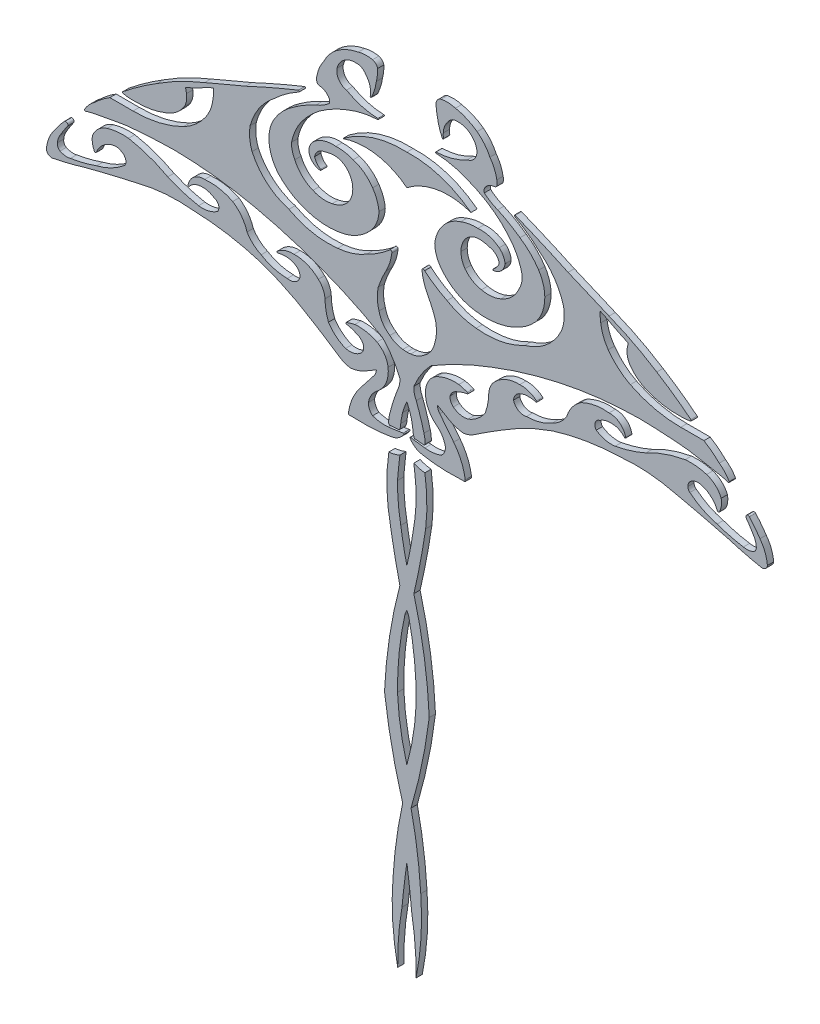
SolidWorks part; units mm, degrees
ref_plane "Front Plane" through (0, 0, 0) normal (0, 0, 1) x (1, 0, 0)
ref_plane "Top Plane" through (0, 0, 0) normal (0, 1, 0) x (1, 0, 0)
ref_plane "Right Plane" through (0, 0, 0) normal (1, 0, 0) x (0, 0, -1)
sketch "Sketch1" plane through (0, 0, 0) normal (0, 0, 1) x (1, 0, 0)
  line L0 (-378.0119, -291.6757) -> (723.9881, -291.6757) construction
  line L1 (0, 181.751) -> (0, -1116.5704) construction
  arc A0 (0, 0) -> (-102.3189, 16.8185) centre (-66.4769, -84.7774) ccw
  arc A1 (-102.3189, 16.8185) -> (0, 49.2353) centre (-6.7694, -107.0837) cw
  arc A2 (-46.483, 72.6334) -> (-96.5623, 86.847) centre (-42.9515, 180.406) cw
  arc A3 (-96.5623, 86.847) -> (-111.4389, 109.7382) centre (-92.7564, 105.6) cw
  arc A4 (-111.4389, 109.7382) -> (-82.2435, 131.9754) centre (-82.989, 102.6702) cw
  arc A5 (-82.2435, 131.9754) -> (-65.2385, 123.0329) centre (-80.0803, 115.4492) cw
  arc A6 (-65.2385, 123.0329) -> (-58.1804, 104.9836) centre (-86.4069, 104.3505) cw
  arc A7 (-58.1804, 104.9836) -> (-58.5682, 97.2174) centre (-81.9092, 102.2759) cw
  arc A8 (-58.5682, 97.2174) -> (-56.4425, 97.2174) centre (-57.5054, 97.2174) ccw
  arc A9 (-56.4425, 97.2174) -> (-48.7691, 122.5661) centre (-133.535, 134.3902) ccw
  arc A10 (-48.7691, 122.5661) -> (-46.7767, 141.444) centre (-115.5182, 139.1549) ccw
  arc A11 (-46.7767, 141.444) -> (-54.7054, 149.7875) centre (-57.8622, 138.8487) ccw
  arc A12 (-54.7054, 149.7875) -> (-77.6132, 148.8108) centre (-64.0956, 100.8971) ccw
  arc A13 (-112.1193, 133.6364) -> (-77.6132, 148.8108) centre (-61.5639, 65.4951) cw
  arc A14 (-112.1193, 133.6364) -> (-132.6666, 108.4613) centre (-72.6732, 80.4688) ccw
  arc A15 (-132.6666, 108.4613) -> (-143.7211, 82.666) centre (-82.6313, 71.7525) ccw
  arc A16 (-143.7211, 82.666) -> (-143.3742, 73.2976) centre (-127.6335, 78.571) ccw
  arc A17 (-143.3742, 73.2976) -> (-137.048, 71.0587) centre (-137.4037, 80.1106) ccw
  arc A18 (-137.048, 71.0587) -> (-126.2748, 64.5384) centre (-141.3136, 51.8507) cw
  arc A19 (-126.2748, 64.5384) -> (-123.7556, 54.7168) centre (-132.7532, 57.6428) cw
  arc A20 (-123.7556, 54.7168) -> (-145.0294, 41.952) centre (-168.0022, 104.3484) cw
  arc A21 (-145.0294, 41.952) -> (-180.6885, 21.1157) centre (-57.2788, -149.1556) ccw
  arc A22 (-180.6885, 21.1157) -> (-210.51, -8.7424) centre (-124.3326, -64.9924) ccw
  arc A23 (-210.51, -8.7424) -> (-220.3219, -40.8055) centre (-159.94, -41.7507) ccw
  arc A24 (-220.3219, -40.8055) -> (-206.0173, -82.3392) centre (-155.8049, -41.8154) ccw
  arc A25 (-206.0173, -82.3392) -> (-171.1908, -107.3688) centre (-131.9958, -16.0886) ccw
  arc A26 (-171.1908, -107.3688) -> (-108.8299, -115.592) centre (-126.2265, -6.9498) ccw
  arc A27 (-108.8299, -115.592) -> (-57.2788, -87.3333) centre (-119.7423, -34.5346) ccw
  arc A28 (-57.2788, -87.3333) -> (-44.4934, -55.3678) centre (-95.762, -53.4012) ccw
  arc A29 (-44.4934, -55.3678) -> (-54.7054, -27.6212) centre (-102.7057, -61.04) ccw
  arc A30 (-54.7054, -27.6212) -> (-85.7618, -4.1993) centre (-103.0408, -59.4111) ccw
  arc A31 (-85.7618, -4.1993) -> (-113.4484, 0.522) centre (-110.5767, -66.1782) ccw
  arc A32 (-113.4484, 0.522) -> (-147.4372, -9.344) centre (-118.1047, -46.9163) ccw
  arc A33 (-147.4372, -9.344) -> (-156.6796, -26.9832) centre (-132.5866, -28.3663) ccw
  arc A34 (-156.6796, -26.9832) -> (-148.8885, -41.1174) centre (-136.5721, -25.1138) ccw
  arc A35 (-148.8885, -41.1174) -> (-138.6418, -45.2059) centre (-138.1949, -29.2014) ccw
  arc A36 (-138.6418, -45.2059) -> (-137.9867, -43.384) centre (-138.3143, -44.295) ccw
  arc A37 (-137.9867, -43.384) -> (-147.4372, -30.7709) centre (-125.2796, -24.0161) cw
  arc A38 (-147.4372, -30.7709) -> (-131.9958, -16.0886) centre (-129.3273, -34.3561) cw
  arc A39 (-131.9958, -16.0886) -> (-115.5182, -13.2218) centre (-113.7987, -71.8932) cw
  arc A40 (-115.5182, -13.2218) -> (-95.3685, -21.9336) centre (-116.1464, -42.3331) cw
  arc A41 (-95.3685, -21.9336) -> (-86.4069, -45.0164) centre (-119.862, -44.7238) cw
  arc A42 (-86.4069, -45.0164) -> (-92.7564, -65.592) centre (-121.6366, -45.4124) cw
  arc A43 (-92.7564, -65.592) -> (-119.1175, -81.6215) centre (-126.143, -40.377) cw
  arc A44 (-119.1175, -81.6215) -> (-150.1147, -78.7107) centre (-130.2753, -33.9405) cw
  arc A45 (-150.1147, -78.7107) -> (-179.0485, -50.7531) centre (-130.1774, -29.1264) cw
  arc A46 (-179.0485, -50.7531) -> (-184.2649, -29.2014) centre (-143.3525, -30.7061) cw
  arc A47 (-184.2649, -29.2014) -> (-168.8065, 6.5252) centre (-88.1202, -49.5943) cw
  arc A48 (-168.8065, 6.5252) -> (-139.8467, 36.025) centre (-48.582, -82.5332) cw
  arc A49 (-139.8467, 36.025) -> (-96.2943, 59.6302) centre (-32.3236, -110.3788) cw
  arc A50 (-96.2943, 59.6302) -> (-46.4858, 70.9563) centre (-40.0511, -72.5255) cw
  arc A51 (-46.4858, 70.9563) -> (-46.2211, 70.9349) centre (-46.2211, 72.5858) ccw
  arc A52 (-46.483, 72.6334) -> (-46.2211, 70.9349) centre (-46.5389, 71.7553) cw
  arc A53 (-28.3634, -100.6488) -> (-24.094, -102.4231) centre (-26.2287, -101.5359) cw
  arc A54 (-24.094, -102.4231) -> (-33.2933, -131.6216) centre (-105.0337, -92.9706) cw
  arc A55 (-33.2933, -131.6216) -> (-45.6894, -160.3636) centre (125.294, -217.0624) ccw
  arc A56 (-45.6894, -160.3636) -> (-44.4934, -192.7226) centre (16.7734, -174.2566) ccw
  arc A57 (-44.4934, -192.7226) -> (-27.3102, -218.0138) centre (-4.5358, -184.0578) ccw
  arc A58 (-27.3102, -218.0138) -> (-6.3379, -226.8008) centre (-3.4306, -190.4404) ccw
  arc A59 (-6.3379, -226.8008) -> (0, -227.3075) centre (-0.7491, -196.7902) ccw
  arc A60 (-28.3634, -100.6488) -> (-64.0956, -123.9892) centre (-139.3306, 30.2111) cw
  arc A61 (-64.0956, -123.9892) -> (-110.5767, -139.0492) centre (-120.227, -30.0051) cw
  arc A62 (-110.5767, -139.0492) -> (-188.4818, -123.9892) centre (-125.8688, -9.1241) cw
  arc A63 (-188.4818, -123.9892) -> (-247.3115, -73.6071) centre (-163.5773, -35.3711) cw
  arc A64 (-247.3115, -73.6071) -> (-250.409, -39.3794) centre (-184.2686, -50.6478) cw
  arc A65 (-250.409, -39.3794) -> (-212.6275, 16.8185) centre (-147.4311, -67.8118) cw
  arc A66 (-212.6275, 16.8185) -> (-172.1247, 46.3083) centre (-80.3177, -122.3429) cw
  arc A67 (-172.1247, 46.3083) -> (-173.2239, 48.3275) centre (-172.6743, 47.3179) ccw
  arc A68 (-173.2239, 48.3275) -> (-257.5095, 11.6916) centre (435.89, -1468.2903) ccw
  arc A69 (-257.5095, 11.6916) -> (-322.9676, -16.0886) centre (2952.8946, -7643.9409) ccw
  arc A70 (-322.9676, -16.0886) -> (-399.1204, -55.3678) centre (-159.0907, -427.2672) ccw
  arc A71 (-399.1204, -55.3678) -> (-453.5942, -93.927) centre (-117.005, -511.6792) ccw
  arc A72 (-453.5942, -93.927) -> (-452.6062, -96.3822) centre (-452.8555, -95.0561) ccw
  arc A73 (-452.6062, -96.3822) -> (-433.1043, -97.7111) centre (-437.833, -23.3425) ccw
  arc A74 (-433.1043, -97.7111) -> (-384.6385, -88.7149) centre (-430.4793, 23.1966) ccw
  arc A75 (-384.6385, -88.7149) -> (-355.5562, -65.592) centre (-403.0323, -35.7301) ccw
  arc A76 (-355.5562, -65.592) -> (-351.9385, -45.7392) centre (-381.8686, -50.5412) ccw
  arc A77 (-351.9385, -45.7392) -> (-353.424, -39.4478) centre (-419.2638, -58.3153) ccw
  arc A78 (-353.424, -39.4478) -> (-352.9033, -37.7713) centre (-352.4454, -38.8327) cw
  arc A79 (-352.9033, -37.7713) -> (-330.511, -27.14) centre (-489.5739, 278.9889) ccw
  arc A80 (-330.511, -27.14) -> (-310.3, -16.9518) centre (-192.7234, -275.3373) cw
  arc A81 (-310.3, -16.9518) -> (-308.6385, -18.1987) centre (-309.6332, -17.7937) cw
  arc A82 (-308.6385, -18.1987) -> (-309.6591, -32.0838) centre (-382.7732, -19.7292) cw
  arc A83 (-309.6591, -32.0838) -> (-321.5963, -63.2462) centre (-376.3675, -24.3977) cw
  arc A84 (-321.5963, -63.2462) -> (-356.8472, -93.9416) centre (-402.6423, -5.7614) cw
  arc A85 (-356.8472, -93.9416) -> (-437.4533, -112.6193) centre (-435.8843, 63.8822) cw
  arc A86 (-474.4649, -112.6159) -> (-437.4533, -112.6193) centre (-456.149, -2215.7829) cw
  arc A87 (-474.4649, -112.6159) -> (-498.9767, -131.6216) centre (-402.2878, -231.0127) ccw
  arc A88 (-498.9767, -131.6216) -> (-514.9281, -149.1556) centre (-469.5713, -174.3956) ccw
  arc A89 (-514.9281, -149.1556) -> (-513.7614, -150.994) centre (-513.4255, -149.4915) ccw
  arc A90 (-513.7614, -150.994) -> (-499.013, -147.1765) centre (-476.0319, -266.358) cw
  arc A91 (-499.013, -147.1765) -> (-447.9623, -137.9258) centre (-61.5072, -2416.1126) cw
  arc A92 (-447.9623, -137.9258) -> (-371.6597, -133.5663) centre (-355.7068, -1082.7056) cw
  arc A93 (-371.6597, -133.5663) -> (-243.1096, -148.1576) centre (-379.2463, -773.9686) cw
  arc A94 (-243.1096, -148.1576) -> (-136.5601, -180.1319) centre (-396.1368, -851.6132) cw
  arc A95 (-136.5601, -180.1319) -> (-38.6116, -226.8008) centre (-345.7415, -745.2835) cw
  arc A96 (-38.6116, -226.8008) -> (-11.1563, -269.0901) centre (-137.0544, -320.7693) cw
  arc A97 (-11.1563, -269.0901) -> (-14.9592, -287.0748) centre (-45.3904, -271.2455) cw
  arc A98 (-14.9592, -287.0748) -> (-27.3102, -325.9538) centre (328.1017, -417.4587) ccw
  arc A99 (-27.3102, -325.9538) -> (-28.9907, -340.31) centre (16.6879, -338.3805) ccw
  arc A100 (-28.9907, -340.31) -> (-25.9215, -342.1446) centre (-26.8538, -340.2198) ccw
  arc A101 (-25.9215, -342.1446) -> (-12.1152, -340.925) centre (7.634, -643.2344) cw
  arc A102 (-12.1152, -340.925) -> (-9.7768, -331.0515) centre (-32.2662, -330.9388) ccw
  arc A103 (-9.7768, -331.0515) -> (-6.8871, -314.6825) centre (153.846, -351.4973) cw
  arc A104 (-6.8871, -314.6825) -> (0, -296.1273) centre (110.3835, -347.6537) cw
  arc A105 (-546.9979, -181.6699) -> (-541.6226, -185.4005) centre (-544.751, -184.1704) cw
  arc A106 (-541.6226, -185.4005) -> (-553.8172, -204.2541) centre (-370.8434, -309.2326) ccw
  arc A107 (-553.8172, -204.2541) -> (-557.9546, -216.4656) centre (-532.8079, -218.1788) ccw
  arc A108 (-557.9546, -216.4656) -> (-554.0175, -226.3081) centre (-548.9709, -218.5808) ccw
  arc A109 (-554.0175, -226.3081) -> (-537.4258, -228.1829) centre (-543.0443, -203.5503) ccw
  arc A110 (-537.4258, -228.1829) -> (-495.4838, -217.4557) centre (-574.7153, 4.9721) ccw
  arc A111 (-495.4838, -217.4557) -> (-451.9725, -195.5366) centre (-522.1017, -110.4705) ccw
  arc A112 (-451.9725, -195.5366) -> (-448.7453, -188.9198) centre (-456.8054, -189.084) ccw
  arc A113 (-448.7453, -188.9198) -> (-455.9129, -177.8874) centre (-460.8784, -188.958) ccw
  arc A114 (-455.9129, -177.8874) -> (-469.5712, -175.9442) centre (-464.8457, -191.7016) ccw
  arc A115 (-469.5712, -175.9442) -> (-486.1646, -184.8547) centre (-462.4849, -209.0464) ccw
  arc A116 (-486.1646, -184.8547) -> (-495.9177, -199.1096) centre (-465.7591, -209.2798) ccw
  arc A117 (-495.9177, -199.1096) -> (-499.239, -198.8346) centre (-497.4939, -197.9516) cw
  arc A118 (-499.239, -198.8346) -> (-502.0431, -178.553) centre (-471.1332, -184.6141) cw
  arc A119 (-502.0431, -178.553) -> (-478.8201, -157.2688) centre (-467.8697, -192.5281) cw
  arc A120 (-478.8201, -157.2688) -> (-444.5362, -153.9251) centre (-453.5928, -238.498) cw
  arc A121 (-444.5362, -153.9251) -> (-381.8685, -175.9442) centre (-479.3229, -353.1176) cw
  arc A122 (-381.8685, -175.9442) -> (-332.687, -191.2123) centre (-292.7207, 24.3729) ccw
  arc A123 (-332.687, -191.2123) -> (-302.4598, -184.1704) centre (-326.5266, -149.2604) ccw
  arc A124 (-302.4598, -184.1704) -> (-308.0001, -167.829) centre (-310.4959, -177.785) ccw
  arc A125 (-308.0001, -167.829) -> (-329.0845, -162.5435) centre (-325.7742, -194.035) ccw
  arc A126 (-329.0845, -162.5435) -> (-347.3525, -171.4954) centre (-327.7599, -188.3623) ccw
  arc A127 (-347.3525, -171.4954) -> (-349.4552, -170.6422) centre (-348.4039, -171.0688) cw
  arc A128 (-349.4552, -170.6422) -> (-322.9675, -150.0298) centre (-324.1731, -175.8057) cw
  arc A129 (-322.9675, -150.0298) -> (-278.1809, -158.1617) centre (-314.2906, -229.64) cw
  arc A130 (-278.1809, -158.1617) -> (-255.2999, -188.9198) centre (-309.0464, -205.0123) cw
  arc A131 (-255.2999, -188.9198) -> (-232.7724, -209.0464) centre (-211.692, -162.7808) ccw
  arc A132 (-232.7724, -209.0464) -> (-190.9927, -221.0018) centre (-190.8173, -141.4087) ccw
  arc A133 (-190.9927, -221.0018) -> (-170.3621, -208.5523) centre (-186.9022, -204.4617) ccw
  arc A134 (-170.3621, -208.5523) -> (-180.6884, -194.7346) centre (-185.849, -209.3587) ccw
  arc A135 (-180.6884, -194.7346) -> (-196.869, -191.9889) centre (-193.236, -219.6286) ccw
  arc A136 (-196.869, -191.9889) -> (-206.3346, -193.5424) centre (-196.3553, -224.7328) ccw
  arc A137 (-206.3346, -193.5424) -> (-207.0314, -191.3643) centre (-206.3922, -192.3603) cw
  arc A138 (-207.0314, -191.3643) -> (-180.2938, -182.1946) centre (-182.3313, -219.8202) cw
  arc A139 (-180.2938, -182.1946) -> (-141.3135, -197.3674) centre (-178.2722, -234.6594) cw
  arc A140 (-141.3135, -197.3674) -> (-130.8216, -219.0498) centre (-161.967, -220.7412) cw
  arc A141 (-130.8216, -219.0498) -> (-125.2795, -248.6402) centre (-40.8883, -217.5202) ccw
  arc A142 (-125.2795, -248.6402) -> (-97.7824, -271.2456) centre (-77.077, -218.0333) ccw
  arc A143 (-97.7824, -271.2456) -> (-74.1073, -266.1529) centre (-91.1675, -244.42) ccw
  arc A144 (-74.1073, -266.1529) -> (-69.0196, -253.4372) centre (-82.5483, -255.3999) ccw
  arc A145 (-69.0196, -253.4372) -> (-80.0802, -242.2424) centre (-85.1612, -258.3239) ccw
  arc A146 (-80.0802, -242.2424) -> (-96.8944, -236.93) centre (-104.4346, -290.0603) ccw
  arc A147 (-96.8944, -236.93) -> (-96.4492, -234.6594) centre (-96.4372, -235.8407) cw
  arc A148 (-96.4492, -234.6594) -> (-82.9889, -230.6296) centre (-60.5855, -329.9571) cw
  arc A149 (-82.9889, -230.6296) -> (-47.776, -237.3531) centre (-77.1991, -295.8784) cw
  arc A150 (-47.776, -237.3531) -> (-30.0199, -263.5266) centre (-64.4046, -267.7436) cw
  arc A151 (-30.0199, -263.5266) -> (-47.7694, -305.183) centre (-74.868, -269.0268) cw
  arc A152 (-47.7694, -305.183) -> (-61.5638, -327.8841) centre (-24.1499, -335.0771) ccw
  arc A153 (-61.5638, -327.8841) -> (-54.7053, -342.8091) centre (-42.9012, -328.3464) ccw
  arc A154 (-54.7053, -342.8091) -> (-28.7935, -345.6118) centre (-35.7289, -288.5491) ccw
  arc A155 (-28.7935, -345.6118) -> (-5.944, -342.3488) centre (-95.4238, 202.6023) ccw
  arc A156 (-5.944, -342.3488) -> (-5.3248, -344.2626) centre (-5.8269, -343.368) cw
  arc A157 (-5.3248, -344.2626) -> (-24.7836, -356.8717) centre (-28.7786, -329.3874) cw
  arc A158 (-24.7836, -356.8717) -> (-81.909, -360.4078) centre (-67.801, -125.1247) cw
  arc A159 (-81.909, -360.4078) -> (-92.7562, -360.4078) centre (-87.3326, 307.53) cw
  arc A160 (-92.7562, -360.4078) -> (-93.2861, -357.5391) centre (-83.2007, -357.1596) cw
  arc A161 (-93.2861, -357.5391) -> (-74.7697, -314.5574) centre (-3.2122, -370.8635) cw
  arc A162 (-74.7697, -314.5574) -> (-52.591, -286.2692) centre (-8117.4811, 6013.9738) ccw
  arc A163 (-52.591, -286.2692) -> (-48.7691, -276.3887) centre (-65.6972, -275.5202) ccw
  arc A164 (-48.7691, -276.3887) -> (-67.801, -287.571) centre (493.4726, -1221.0455) ccw
  arc A165 (-67.801, -287.571) -> (-90.3839, -294.4032) centre (-95.8264, -235.675) cw
  arc A166 (-90.3839, -294.4032) -> (-107.7289, -287.7163) centre (-84.6165, -253.6042) cw
  arc A167 (-107.7289, -287.7163) -> (-151.0092, -259.9062) centre (-699.8204, -1161.5955) ccw
  arc A168 (-151.0092, -259.9062) -> (-232.7724, -220.0581) centre (-358.0183, -580.8543) ccw
  arc A169 (-232.7724, -220.0581) -> (-340.5656, -202.0535) centre (-352.5017, -605.1942) ccw
  arc A170 (-340.5656, -202.0535) -> (-428.5206, -208.5523) centre (-366.1303, -454.5047) ccw
  arc A171 (-428.5206, -208.5523) -> (-512.696, -228.6998) centre (35.2634, -2332.1267) ccw
  arc A172 (-512.696, -228.6998) -> (-566.4385, -242.2428) centre (-670.7267, 285.0099) cw
  arc A173 (-566.4385, -242.2428) -> (-575.884, -234.6603) centre (-567.2492, -233.5783) cw
  arc A174 (-575.884, -234.6603) -> (-564.0087, -203.5503) centre (-516.9046, -239.3525) cw
  arc A175 (-564.0087, -203.5503) -> (-546.9979, -181.6699) centre (-406.0443, -308.8063) cw
  arc A176 (-28.7935, -379.9019) -> (-11.1563, -375.3609) centre (-31.6686, -332.2134) ccw
  arc A177 (-11.1563, -375.3609) -> (-14.9592, -412.6536) centre (1042.6478, -501.6644) ccw
  arc A178 (-14.9396, -412.4201) -> (-9.7768, -471.8542) centre (293.8212, -415.5408) ccw
  arc A179 (-9.7768, -471.8542) -> (0, -522.6343) centre (553.3175, -389.7715) ccw
  arc A180 (-28.7935, -379.9019) -> (-30.0199, -456.9184) centre (259.1866, -423.0059) ccw
  arc A181 (-30.0199, -456.9184) -> (-11.1563, -555.9992) centre (1181.1468, -277.6643) ccw
  arc A182 (-11.1563, -555.9992) -> (-35.7289, -714.9618) centre (709.8449, -748.8329) ccw
  arc A183 (-35.7289, -714.9618) -> (-6.6916, -854.7494) centre (826.5855, -608.748) ccw
  arc A184 (-6.6916, -854.7494) -> (-22.1757, -965.4265) centre (686.6853, -1008.1767) ccw
  arc A185 (-22.1757, -965.4265) -> (-14.6303, -1085.8567) centre (407.7374, -998.9423) ccw
  arc A186 (-14.6303, -1085.8567) -> (-7.818, -999.1382) centre (437.9689, -1077.7844) cw
  arc A187 (-7.818, -999.1382) -> (0, -933.7557) centre (1375.5739, -1131.3962) cw
  arc A188 (0, -798.4232) -> (-14.9592, -705.6101) centre (389.6137, -688.0148) cw
  arc A189 (-14.9592, -705.6101) -> (-3.2122, -592.5595) centre (484.8265, -700.4067) cw
  arc A190 (-3.2122, -592.5595) -> (0, -584.5298) centre (26.2233, -599.6777) cw
  arc A191 (3.2122, -592.5595) -> (0, -584.5298) centre (-26.2233, -599.6777) ccw
  arc A192 (14.9592, -705.6101) -> (3.2122, -592.5595) centre (-484.8265, -700.4067) ccw
  arc A193 (0, -798.4232) -> (14.9592, -705.6101) centre (-389.6137, -688.0148) ccw
  arc A194 (7.818, -999.1382) -> (0, -933.7557) centre (-1375.5739, -1131.3962) ccw
  arc A195 (14.6303, -1085.8567) -> (7.818, -999.1382) centre (-437.9689, -1077.7844) ccw
  arc A196 (22.1757, -965.4265) -> (14.6303, -1085.8567) centre (-407.7374, -998.9423) cw
  arc A197 (6.6916, -854.7494) -> (22.1757, -965.4265) centre (-686.6853, -1008.1767) cw
  arc A198 (35.7289, -714.9618) -> (6.6916, -854.7494) centre (-826.5855, -608.748) cw
  arc A199 (11.1563, -555.9992) -> (35.7289, -714.9618) centre (-709.8449, -748.8329) cw
  arc A200 (30.0199, -456.9184) -> (11.1563, -555.9992) centre (-1181.1468, -277.6643) cw
  arc A201 (28.7935, -379.9019) -> (30.0199, -456.9184) centre (-259.1866, -423.0059) cw
  arc A202 (9.7768, -471.8542) -> (0, -522.6343) centre (-553.3175, -389.7715) cw
  arc A203 (14.9396, -412.4201) -> (9.7768, -471.8542) centre (-293.8212, -415.5408) cw
  arc A204 (11.1563, -375.3609) -> (14.9592, -412.6536) centre (-1042.6478, -501.6644) cw
  arc A205 (28.7935, -379.9019) -> (11.1563, -375.3609) centre (31.6686, -332.2134) cw
  arc A206 (564.0087, -203.5503) -> (546.9979, -181.6699) centre (406.0443, -308.8063) ccw
  arc A207 (575.884, -234.6603) -> (564.0087, -203.5503) centre (516.9046, -239.3525) ccw
  arc A208 (566.4385, -242.2428) -> (575.884, -234.6603) centre (567.2492, -233.5783) ccw
  arc A209 (512.696, -228.6998) -> (566.4385, -242.2428) centre (670.7267, 285.0099) ccw
  arc A210 (428.5206, -208.5523) -> (512.696, -228.6998) centre (-35.2634, -2332.1267) cw
  arc A211 (340.5656, -202.0535) -> (428.5206, -208.5523) centre (366.1303, -454.5047) cw
  arc A212 (232.7724, -220.0581) -> (340.5656, -202.0535) centre (352.5017, -605.1942) cw
  arc A213 (151.0092, -259.9062) -> (232.7724, -220.0581) centre (358.0183, -580.8543) cw
  arc A214 (107.7289, -287.7163) -> (151.0092, -259.9062) centre (699.8204, -1161.5955) cw
  arc A215 (90.3839, -294.4032) -> (107.7289, -287.7163) centre (84.6165, -253.6042) ccw
  arc A216 (67.801, -287.571) -> (90.3839, -294.4032) centre (95.8264, -235.675) ccw
  arc A217 (48.7691, -276.3887) -> (67.801, -287.571) centre (-493.4726, -1221.0455) cw
  arc A218 (52.591, -286.2692) -> (48.7691, -276.3887) centre (65.6972, -275.5202) cw
  arc A219 (74.7697, -314.5574) -> (52.591, -286.2692) centre (8117.4811, 6013.9738) cw
  arc A220 (93.2861, -357.5391) -> (74.7697, -314.5574) centre (3.2122, -370.8635) ccw
  arc A221 (92.7562, -360.4078) -> (93.2861, -357.5391) centre (83.2007, -357.1596) ccw
  arc A222 (81.909, -360.4078) -> (92.7562, -360.4078) centre (87.3326, 307.53) ccw
  arc A223 (24.7836, -356.8717) -> (81.909, -360.4078) centre (67.801, -125.1247) ccw
  arc A224 (5.3248, -344.2626) -> (24.7836, -356.8717) centre (28.7786, -329.3874) ccw
  arc A225 (5.944, -342.3488) -> (5.3248, -344.2626) centre (5.8269, -343.368) ccw
  arc A226 (28.7935, -345.6118) -> (5.944, -342.3488) centre (95.4238, 202.6023) cw
  arc A227 (54.7053, -342.8091) -> (28.7935, -345.6118) centre (35.7289, -288.5491) cw
  arc A228 (61.5638, -327.8841) -> (54.7053, -342.8091) centre (42.9012, -328.3464) cw
  arc A229 (47.7694, -305.183) -> (61.5638, -327.8841) centre (24.1499, -335.0771) cw
  arc A230 (30.0199, -263.5266) -> (47.7694, -305.183) centre (74.868, -269.0268) ccw
  arc A231 (47.776, -237.3531) -> (30.0199, -263.5266) centre (64.4046, -267.7436) ccw
  arc A232 (82.9889, -230.6296) -> (47.776, -237.3531) centre (77.1991, -295.8784) ccw
  arc A233 (96.4492, -234.6594) -> (82.9889, -230.6296) centre (60.5855, -329.9571) ccw
  arc A234 (96.8944, -236.93) -> (96.4492, -234.6594) centre (96.4372, -235.8407) ccw
  arc A235 (80.0802, -242.2424) -> (96.8944, -236.93) centre (104.4346, -290.0603) cw
  arc A236 (69.0196, -253.4372) -> (80.0802, -242.2424) centre (85.1612, -258.3239) cw
  arc A237 (74.1073, -266.1529) -> (69.0196, -253.4372) centre (82.5483, -255.3999) cw
  arc A238 (97.7824, -271.2456) -> (74.1073, -266.1529) centre (91.1675, -244.42) cw
  arc A239 (125.2795, -248.6402) -> (97.7824, -271.2456) centre (77.077, -218.0333) cw
  arc A240 (130.8216, -219.0498) -> (125.2795, -248.6402) centre (40.8883, -217.5202) cw
  arc A241 (141.3135, -197.3674) -> (130.8216, -219.0498) centre (161.967, -220.7412) ccw
  arc A242 (180.2938, -182.1946) -> (141.3135, -197.3674) centre (178.2722, -234.6594) ccw
  arc A243 (207.0314, -191.3643) -> (180.2938, -182.1946) centre (182.3313, -219.8202) ccw
  arc A244 (206.3346, -193.5424) -> (207.0314, -191.3643) centre (206.3922, -192.3603) ccw
  arc A245 (196.869, -191.9889) -> (206.3346, -193.5424) centre (196.3553, -224.7328) cw
  arc A246 (180.6884, -194.7346) -> (196.869, -191.9889) centre (193.236, -219.6286) cw
  arc A247 (170.3621, -208.5523) -> (180.6884, -194.7346) centre (185.849, -209.3587) cw
  arc A248 (190.9927, -221.0018) -> (170.3621, -208.5523) centre (186.9022, -204.4617) cw
  arc A249 (232.7724, -209.0464) -> (190.9927, -221.0018) centre (190.8173, -141.4087) cw
  arc A250 (255.2999, -188.9198) -> (232.7724, -209.0464) centre (211.692, -162.7808) cw
  arc A251 (278.1809, -158.1617) -> (255.2999, -188.9198) centre (309.0464, -205.0123) ccw
  arc A252 (322.9675, -150.0298) -> (278.1809, -158.1617) centre (314.2906, -229.64) ccw
  arc A253 (349.4552, -170.6422) -> (322.9675, -150.0298) centre (324.1731, -175.8057) ccw
  arc A254 (347.3525, -171.4954) -> (349.4552, -170.6422) centre (348.4039, -171.0688) ccw
  arc A255 (329.0845, -162.5435) -> (347.3525, -171.4954) centre (327.7599, -188.3623) cw
  arc A256 (308.0001, -167.829) -> (329.0845, -162.5435) centre (325.7742, -194.035) cw
  arc A257 (302.4598, -184.1704) -> (308.0001, -167.829) centre (310.4959, -177.785) cw
  arc A258 (332.687, -191.2123) -> (302.4598, -184.1704) centre (326.5266, -149.2604) cw
  arc A259 (381.8685, -175.9442) -> (332.687, -191.2123) centre (292.7207, 24.3729) cw
  arc A260 (444.5362, -153.9251) -> (381.8685, -175.9442) centre (479.3229, -353.1176) ccw
  arc A261 (478.8201, -157.2688) -> (444.5362, -153.9251) centre (453.5928, -238.498) ccw
  arc A262 (502.0431, -178.553) -> (478.8201, -157.2688) centre (467.8697, -192.5281) ccw
  arc A263 (499.239, -198.8346) -> (502.0431, -178.553) centre (471.1332, -184.6141) ccw
  arc A264 (495.9177, -199.1096) -> (499.239, -198.8346) centre (497.4939, -197.9516) ccw
  arc A265 (486.1646, -184.8547) -> (495.9177, -199.1096) centre (465.7591, -209.2798) cw
  arc A266 (469.5712, -175.9442) -> (486.1646, -184.8547) centre (462.4849, -209.0464) cw
  arc A267 (455.9129, -177.8874) -> (469.5712, -175.9442) centre (464.8457, -191.7016) cw
  arc A268 (448.7453, -188.9198) -> (455.9129, -177.8874) centre (460.8784, -188.958) cw
  arc A269 (451.9725, -195.5366) -> (448.7453, -188.9198) centre (456.8054, -189.084) cw
  arc A270 (495.4838, -217.4557) -> (451.9725, -195.5366) centre (522.1017, -110.4705) cw
  arc A271 (537.4258, -228.1829) -> (495.4838, -217.4557) centre (574.7153, 4.9721) cw
  arc A272 (554.0175, -226.3081) -> (537.4258, -228.1829) centre (543.0443, -203.5503) cw
  arc A273 (557.9546, -216.4656) -> (554.0175, -226.3081) centre (548.9709, -218.5808) cw
  arc A274 (553.8172, -204.2541) -> (557.9546, -216.4656) centre (532.8079, -218.1788) cw
  arc A275 (541.6226, -185.4005) -> (553.8172, -204.2541) centre (370.8434, -309.2326) cw
  arc A276 (546.9979, -181.6699) -> (541.6226, -185.4005) centre (544.751, -184.1704) ccw
  arc A277 (6.8871, -314.6825) -> (0, -296.1273) centre (-110.3835, -347.6537) ccw
  arc A278 (9.7768, -331.0515) -> (6.8871, -314.6825) centre (-153.846, -351.4973) ccw
  arc A279 (12.1152, -340.925) -> (9.7768, -331.0515) centre (32.2662, -330.9388) cw
  arc A280 (25.9215, -342.1446) -> (12.1152, -340.925) centre (-7.634, -643.2344) ccw
  arc A281 (28.9907, -340.31) -> (25.9215, -342.1446) centre (26.8538, -340.2198) cw
  arc A282 (27.3102, -325.9538) -> (28.9907, -340.31) centre (-16.6879, -338.3805) cw
  arc A283 (14.9592, -287.0748) -> (27.3102, -325.9538) centre (-328.1017, -417.4587) cw
  arc A284 (11.1563, -269.0901) -> (14.9592, -287.0748) centre (45.3904, -271.2455) ccw
  arc A285 (38.6116, -226.8008) -> (11.1563, -269.0901) centre (137.0544, -320.7693) ccw
  arc A286 (136.5601, -180.1319) -> (38.6116, -226.8008) centre (345.7415, -745.2835) ccw
  arc A287 (243.1096, -148.1576) -> (136.5601, -180.1319) centre (396.1368, -851.6132) ccw
  arc A288 (371.6597, -133.5663) -> (243.1096, -148.1576) centre (379.2463, -773.9686) ccw
  arc A289 (447.9623, -137.9258) -> (371.6597, -133.5663) centre (355.7068, -1082.7056) ccw
  arc A290 (499.013, -147.1765) -> (447.9623, -137.9258) centre (61.5072, -2416.1126) ccw
  arc A291 (513.7614, -150.994) -> (499.013, -147.1765) centre (476.0319, -266.358) ccw
  arc A292 (514.9281, -149.1556) -> (513.7614, -150.994) centre (513.4255, -149.4915) cw
  arc A293 (498.9767, -131.6216) -> (514.9281, -149.1556) centre (469.5713, -174.3956) cw
  arc A294 (474.4649, -112.6159) -> (498.9767, -131.6216) centre (402.2878, -231.0127) cw
  arc A295 (474.4649, -112.6159) -> (437.4533, -112.6193) centre (456.149, -2215.7829) ccw
  arc A296 (356.8472, -93.9416) -> (437.4533, -112.6193) centre (435.8843, 63.8822) ccw
  arc A297 (321.5963, -63.2462) -> (356.8472, -93.9416) centre (402.6423, -5.7614) ccw
  arc A298 (309.6591, -32.0838) -> (321.5963, -63.2462) centre (376.3675, -24.3977) ccw
  arc A299 (308.6385, -18.1987) -> (309.6591, -32.0838) centre (382.7732, -19.7292) ccw
  arc A300 (310.3, -16.9518) -> (308.6385, -18.1987) centre (309.6332, -17.7937) ccw
  arc A301 (330.511, -27.14) -> (310.3, -16.9518) centre (192.7234, -275.3373) ccw
  arc A302 (352.9033, -37.7713) -> (330.511, -27.14) centre (489.5739, 278.9889) cw
  arc A303 (353.424, -39.4478) -> (352.9033, -37.7713) centre (352.4454, -38.8327) ccw
  arc A304 (351.9385, -45.7392) -> (353.424, -39.4478) centre (419.2638, -58.3153) cw
  arc A305 (355.5562, -65.592) -> (351.9385, -45.7392) centre (381.8686, -50.5412) cw
  arc A306 (384.6385, -88.7149) -> (355.5562, -65.592) centre (403.0323, -35.7301) cw
  arc A307 (433.1043, -97.7111) -> (384.6385, -88.7149) centre (430.4793, 23.1966) cw
  arc A308 (452.6062, -96.3822) -> (433.1043, -97.7111) centre (437.833, -23.3425) cw
  arc A309 (453.5942, -93.927) -> (452.6062, -96.3822) centre (452.8555, -95.0561) cw
  arc A310 (399.1204, -55.3678) -> (453.5942, -93.927) centre (117.005, -511.6792) cw
  arc A311 (322.9676, -16.0886) -> (399.1204, -55.3678) centre (159.0907, -427.2672) cw
  arc A312 (257.5095, 11.6916) -> (322.9676, -16.0886) centre (-2952.8946, -7643.9409) cw
  arc A313 (173.2239, 48.3275) -> (257.5095, 11.6916) centre (-435.89, -1468.2903) cw
  arc A314 (172.1247, 46.3083) -> (173.2239, 48.3275) centre (172.6743, 47.3179) cw
  arc A315 (212.6275, 16.8185) -> (172.1247, 46.3083) centre (80.3177, -122.3429) ccw
  arc A316 (250.409, -39.3794) -> (212.6275, 16.8185) centre (147.4311, -67.8118) ccw
  arc A317 (247.3115, -73.6071) -> (250.409, -39.3794) centre (184.2686, -50.6478) ccw
  arc A318 (188.4818, -123.9892) -> (247.3115, -73.6071) centre (163.5773, -35.3711) ccw
  arc A319 (110.5767, -139.0492) -> (188.4818, -123.9892) centre (125.8688, -9.1241) ccw
  arc A320 (64.0956, -123.9892) -> (110.5767, -139.0492) centre (120.227, -30.0051) ccw
  arc A321 (28.3634, -100.6488) -> (64.0956, -123.9892) centre (139.3306, 30.2111) ccw
  arc A322 (6.3379, -226.8008) -> (0, -227.3075) centre (0.7491, -196.7902) cw
  arc A323 (27.3102, -218.0138) -> (6.3379, -226.8008) centre (3.4306, -190.4404) cw
  arc A324 (44.4934, -192.7226) -> (27.3102, -218.0138) centre (4.5358, -184.0578) cw
  arc A325 (45.6894, -160.3636) -> (44.4934, -192.7226) centre (-16.7734, -174.2566) cw
  arc A326 (33.2933, -131.6216) -> (45.6894, -160.3636) centre (-125.294, -217.0624) cw
  arc A327 (24.094, -102.4231) -> (33.2933, -131.6216) centre (105.0337, -92.9706) ccw
  arc A328 (28.3634, -100.6488) -> (24.094, -102.4231) centre (26.2287, -101.5359) ccw
  arc A329 (46.483, 72.6334) -> (46.2211, 70.9349) centre (46.5389, 71.7553) ccw
  arc A330 (46.4858, 70.9563) -> (46.2211, 70.9349) centre (46.2211, 72.5858) cw
  arc A331 (96.2943, 59.6302) -> (46.4858, 70.9563) centre (40.0511, -72.5255) ccw
  arc A332 (139.8467, 36.025) -> (96.2943, 59.6302) centre (32.3236, -110.3788) ccw
  arc A333 (168.8065, 6.5252) -> (139.8467, 36.025) centre (48.582, -82.5332) ccw
  arc A334 (184.2649, -29.2014) -> (168.8065, 6.5252) centre (88.1202, -49.5943) ccw
  arc A335 (179.0485, -50.7531) -> (184.2649, -29.2014) centre (143.3525, -30.7061) ccw
  arc A336 (150.1147, -78.7107) -> (179.0485, -50.7531) centre (130.1774, -29.1264) ccw
  arc A337 (119.1175, -81.6215) -> (150.1147, -78.7107) centre (130.2753, -33.9405) ccw
  arc A338 (92.7564, -65.592) -> (119.1175, -81.6215) centre (126.143, -40.377) ccw
  arc A339 (86.4069, -45.0164) -> (92.7564, -65.592) centre (121.6366, -45.4124) ccw
  arc A340 (95.3685, -21.9336) -> (86.4069, -45.0164) centre (119.862, -44.7238) ccw
  arc A341 (115.5182, -13.2218) -> (95.3685, -21.9336) centre (116.1464, -42.3331) ccw
  arc A342 (131.9958, -16.0886) -> (115.5182, -13.2218) centre (113.7987, -71.8932) ccw
  arc A343 (147.4372, -30.7709) -> (131.9958, -16.0886) centre (129.3273, -34.3561) ccw
  arc A344 (137.9867, -43.384) -> (147.4372, -30.7709) centre (125.2796, -24.0161) ccw
  arc A345 (138.6418, -45.2059) -> (137.9867, -43.384) centre (138.3143, -44.295) cw
  arc A346 (148.8885, -41.1174) -> (138.6418, -45.2059) centre (138.1949, -29.2014) cw
  arc A347 (156.6796, -26.9832) -> (148.8885, -41.1174) centre (136.5721, -25.1138) cw
  arc A348 (147.4372, -9.344) -> (156.6796, -26.9832) centre (132.5866, -28.3663) cw
  arc A349 (113.4484, 0.522) -> (147.4372, -9.344) centre (118.1047, -46.9163) cw
  arc A350 (85.7618, -4.1993) -> (113.4484, 0.522) centre (110.5767, -66.1782) cw
  arc A351 (54.7054, -27.6212) -> (85.7618, -4.1993) centre (103.0408, -59.4111) cw
  arc A352 (44.4934, -55.3678) -> (54.7054, -27.6212) centre (102.7057, -61.04) cw
  arc A353 (57.2788, -87.3333) -> (44.4934, -55.3678) centre (95.762, -53.4012) cw
  arc A354 (108.8299, -115.592) -> (57.2788, -87.3333) centre (119.7423, -34.5346) cw
  arc A355 (171.1908, -107.3688) -> (108.8299, -115.592) centre (126.2265, -6.9498) cw
  arc A356 (206.0173, -82.3392) -> (171.1908, -107.3688) centre (131.9958, -16.0886) cw
  arc A357 (220.3219, -40.8055) -> (206.0173, -82.3392) centre (155.8049, -41.8154) cw
  arc A358 (210.51, -8.7424) -> (220.3219, -40.8055) centre (159.94, -41.7507) cw
  arc A359 (180.6885, 21.1157) -> (210.51, -8.7424) centre (124.3326, -64.9924) cw
  arc A360 (145.0294, 41.952) -> (180.6885, 21.1157) centre (57.2788, -149.1556) cw
  arc A361 (123.7556, 54.7168) -> (145.0294, 41.952) centre (168.0022, 104.3484) ccw
  arc A362 (126.2748, 64.5384) -> (123.7556, 54.7168) centre (132.7532, 57.6428) ccw
  arc A363 (137.048, 71.0587) -> (126.2748, 64.5384) centre (141.3136, 51.8507) ccw
  arc A364 (143.3742, 73.2976) -> (137.048, 71.0587) centre (137.4037, 80.1106) cw
  arc A365 (143.7211, 82.666) -> (143.3742, 73.2976) centre (127.6335, 78.571) cw
  arc A366 (132.6666, 108.4613) -> (143.7211, 82.666) centre (82.6313, 71.7525) cw
  arc A367 (112.1193, 133.6364) -> (132.6666, 108.4613) centre (72.6732, 80.4688) cw
  arc A368 (112.1193, 133.6364) -> (77.6132, 148.8108) centre (61.5639, 65.4951) ccw
  arc A369 (54.7054, 149.7875) -> (77.6132, 148.8108) centre (64.0956, 100.8971) cw
  arc A370 (46.7767, 141.444) -> (54.7054, 149.7875) centre (57.8622, 138.8487) cw
  arc A371 (48.7691, 122.5661) -> (46.7767, 141.444) centre (115.5182, 139.1549) cw
  arc A372 (56.4425, 97.2174) -> (48.7691, 122.5661) centre (133.535, 134.3902) cw
  arc A373 (58.5682, 97.2174) -> (56.4425, 97.2174) centre (57.5054, 97.2174) cw
  arc A374 (58.1804, 104.9836) -> (58.5682, 97.2174) centre (81.9092, 102.2759) ccw
  arc A375 (65.2385, 123.0329) -> (58.1804, 104.9836) centre (86.4069, 104.3505) ccw
  arc A376 (82.2435, 131.9754) -> (65.2385, 123.0329) centre (80.0803, 115.4492) ccw
  arc A377 (111.4389, 109.7382) -> (82.2435, 131.9754) centre (82.989, 102.6702) ccw
  arc A378 (96.5623, 86.847) -> (111.4389, 109.7382) centre (92.7564, 105.6) ccw
  arc A379 (46.483, 72.6334) -> (96.5623, 86.847) centre (42.9515, 180.406) ccw
  arc A380 (102.3189, 16.8185) -> (0, 49.2353) centre (6.7694, -107.0837) ccw
  arc A381 (0, 0) -> (102.3189, 16.8185) centre (66.4769, -84.7774) cw
  point P111 (-46.5191, 72.635)
  point P163 (352.8998, -37.8374)
  point P167 (0, 49.5368)
  point P174 (-353.4432, -39.4659)
  point P359 (-14.6453, -1085.7839)
  point P386 (-46.5465, 70.9042)
  point P398 (0, -933.7557)
  point P620 (-353.4432, -39.5063)
  point P627 (-102.3189, 16.8185)
  point P630 (-173.2239, 48.3275)
  point P784 (-308.6385, -18.2153)
  point P785 (-96.2943, 59.6302)
  point P786 (-452.6062, -96.3822)
  point P787 (-575.8828, -234.6245)
extrude "Boss-Extrude1" add sketch "Sketch1" along normal blind 10 contours A52 A2 A3 A4 A5 A6 A7 A8 A9 A10 A11 A12 A13 A14 A15 A16 A17 A18 A19 A20 A21 A22 A23 A24 A25 A26 A27 A28 A29 A30 A31 A32 A33 A34 A35 A36 A37 A38 A39 A40 A41 A42 A43 A44 A45 A46 A47 A48 A49 A50 A51 | A379 A329 A330 A331 A332 A333 A334 A335 A336 A337 A338 A339 A340 A341 A342 A343 A344 A345 A346 A347 A348 A349 A350 A351 A352 A353 A354 A355 A356 A357 A358 A359 A360 A361 A362 A363 A364 A365 A366 A367 A368 A369 A370 A371 A372 A373 A374 A375 A376 A377 A378 | A321 A328 A327 A326 A325 A324 A323 A322 A59 A58 A57 A56 A55 A54 A53 A60 A61 A62 A63 A64 A65 A66 A67 A68 A69 A70 A71 A72 A73 A74 A75 A76 A77 A78 A79 A80 A81 A82 A83 A84 A85 A86 A87 A88 A89 A90 A91 A92 A93 A94 A95 | A175 A174 A173 A172 A171 A170 A169 A168 A167 A166 A165 A164 A163 A162 A161 A160 A159 A158 A157 A156 A155 A154 A153 A152 A151 A150 A149 A148 A147 A146 A145 A144 A143 A142 A141 A140 A139 A138 A137 A136 A135 A134 A133 A132 A131 A130 A129 A128 A127 A126 A125 | A201 A205 A204 A203 A202 A179 A178 A177 A176 A180 A181 A182 A183 A184 A185 A186 A187 A194 A195 A196 A197 A198 A199 A200 A193 A188 A189 A190 A191 A192 | A381 A380 A1 A0 | A227 A226 A225 A224 A223 A222 A221 A220 A219 A218 A217 A216 A215 A214 A213 A212 A211 A210 A209 A208 A207 A206 A276 A275 A274 A273 A272 A271 A270 A269 A268 A267 A266 A265 A264 A263 A262 A261 A260 A259 A258 A257 A256 A255 A254 A253 A252 A251 A250 A249 A248 A247 A246 A245 A244 A243 A242 A241 A240 A239 A238 A237 A236 A235 A234 A233 A232 A231 A230 A229 A228 region at (-125.9203, -13.825, 0) region at (-29.5691, -109.5736, 0) region at (-546.3061, -186.4111, 0) region at (-17.976, -385.3949, 0) region at (125.9203, -13.825, 0)
